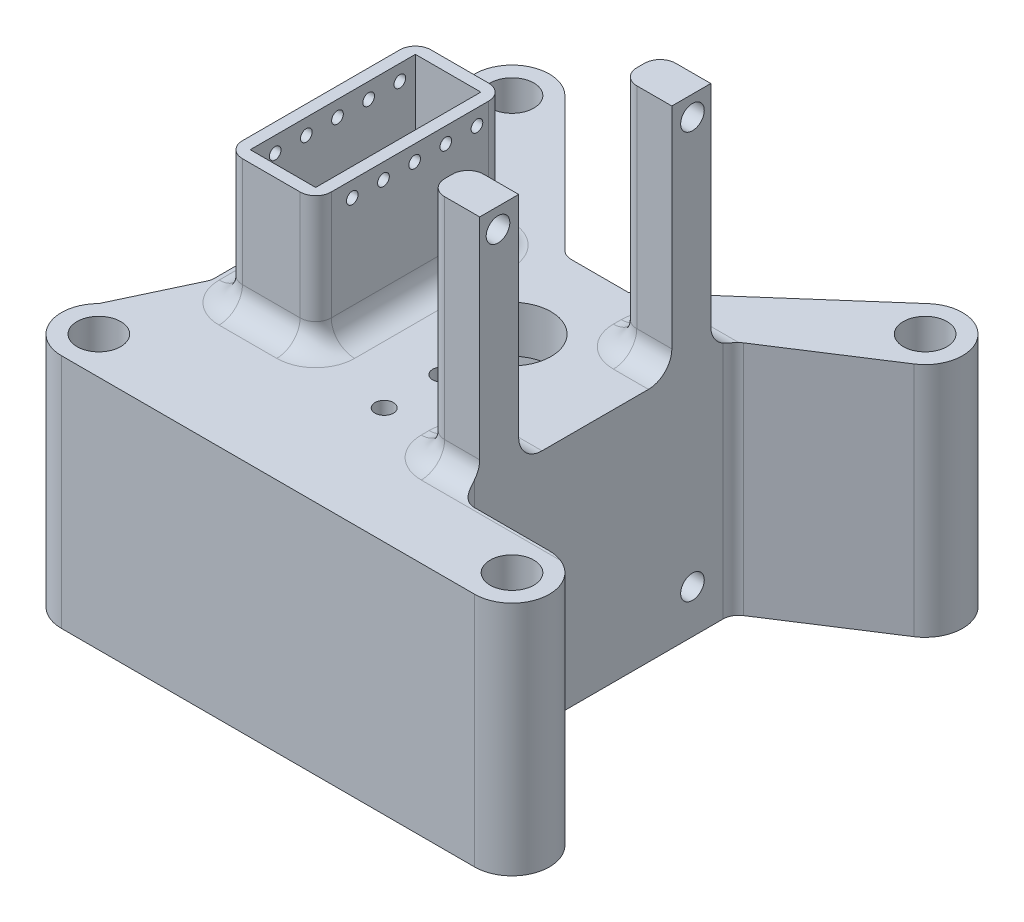
SolidWorks part; units mm, degrees
ref_plane "Front Plane" through (0, 0, 0) normal (0, 0, 1) x (1, 0, 0)
ref_plane "Top Plane" through (0, 0, 0) normal (0, 1, 0) x (1, 0, 0)
ref_plane "Right Plane" through (0, 0, 0) normal (1, 0, 0) x (0, 0, -1)
sketch "Sketch3" plane through (0, 0, 0) normal (0, 1, 0) x (1, 0, 0)
  line L0 (-33.676, -39.772) -> (33.676, -39.772)
  line L1 (-33.676, -33.676) -> (33.676, -33.676) construction
  line L2 (-33.676, -33.676) -> (-33.676, 33.676) construction
  line L3 (-33.676, 33.676) -> (33.676, 33.676) construction
  line L4 (33.676, -33.676) -> (33.676, 33.676) construction
  line L5 (-33.676, -33.676) -> (33.676, 33.676) construction
  line L6 (-33.676, 33.676) -> (33.676, -33.676) construction
  line L7 (10.033, -30.099) -> (-10.033, -30.099)
  line L8 (10.033, -30.099) -> (10.033, 10.033)
  line L9 (10.033, 10.033) -> (3.556, 10.033)
  line L10 (-10.033, -30.099) -> (-10.033, 10.033)
  line L11 (10.033, -30.099) -> (-10.033, 10.033) construction
  line L12 (10.033, 10.033) -> (-10.033, -30.099) construction
  line L13 (33.676, -27.58) -> (18.923, -27.58)
  line L14 (-3.556, 15.367) -> (3.556, 15.367) construction
  line L15 (-3.556, 15.367) -> (-3.556, 10.033)
  line L16 (0, 10.033) -> (3.556, 10.033) construction
  line L17 (3.556, 15.367) -> (3.556, 10.033)
  line L18 (-3.556, 15.367) -> (3.556, 10.033) construction
  line L19 (-3.556, 10.033) -> (3.556, 15.367) construction
  line L20 (-25.781, 10.033) -> (-15.113, 10.033) construction
  line L21 (-25.781, 10.033) -> (-25.781, -16.891) construction
  line L22 (-25.781, -16.891) -> (-15.113, -16.891) construction
  line L23 (-15.113, 10.033) -> (-15.113, -16.891) construction
  line L24 (-25.781, 10.033) -> (-15.113, -16.891) construction
  line L25 (-25.781, -16.891) -> (-15.113, 10.033) construction
  line L26 (18.923, -27.58) -> (18.923, 16.87)
  line L27 (36.9874, 28.5578) -> (18.923, 16.87)
  line L28 (29.6563, 38.259) -> (3.556, 15.367)
  line L31 (0, 10.033) -> (-3.556, 10.033) construction
  line L32 (-29.3669, 37.9879) -> (-6.731, 15.367)
  line L33 (-6.731, 15.367) -> (-3.556, 15.367)
  line L34 (-3.556, 10.033) -> (-10.033, 10.033)
  line L35 (-3.556, 10.033) -> (0, 10.033) construction
  line L36 (3.556, 10.033) -> (0, 10.033) construction
  line L37 (-32.131, -16.891) -> (-32.131, 10.033)
  line L38 (34.003, -24.1637) -> (18.923, -24.1637) construction
  line L39 (34.003, -24.1637) -> (34.003, 13.4537) construction
  line L40 (34.003, 13.4537) -> (18.923, 13.4537) construction
  line L41 (18.923, -24.1637) -> (18.923, 13.4537) construction
  line L42 (34.003, -24.1637) -> (18.923, 13.4537) construction
  line L43 (34.003, 13.4537) -> (18.923, -24.1637) construction
  line L44 (-32.131, 10.033) -> (-39.4519, 31.7268)
  line L45 (-32.131, -16.891) -> (-37.9865, -29.3654)
  circle A0 centre (-33.676, 33.676) radius 3.556
  circle A1 centre (33.676, 33.676) radius 3.556
  circle A2 centre (33.676, -33.676) radius 3.556
  circle A3 centre (-33.676, -33.676) radius 3.556
  circle A4 centre (0, 0) radius 6.35 construction
  circle A5 centre (0, 0) radius 10.033 construction
  circle A6 centre (0, 0) radius 63.5 construction
  arc A7 (33.676, -39.772) -> (33.676, -27.58) centre (33.676, -33.676) ccw
  arc A8 (-39.772, -33.676) -> (-33.676, -39.772) centre (-33.676, -33.676) ccw
  arc A9 (-29.3669, 37.9879) -> (-39.772, 33.676) centre (-33.676, 33.676) ccw
  arc A10 (36.9874, 28.5578) -> (29.6563, 38.259) centre (33.676, 33.676) ccw
  arc A11 (27.58, 33.676) -> (29.3654, 29.3654) centre (33.676, 33.676) ccw construction
  arc A12 (29.6563, 38.259) -> (27.58, 33.676) centre (33.676, 33.676) ccw construction
  arc A13 (29.3654, 29.3654) -> (33.676, 27.58) centre (33.676, 33.676) ccw construction
  arc A14 (33.676, 27.58) -> (36.9874, 28.5578) centre (33.676, 33.676) ccw construction
  arc A15 (-27.58, 33.676) -> (-29.3669, 37.9879) centre (-33.676, 33.676) ccw construction
  arc A16 (-29.3654, 29.3654) -> (-27.58, 33.676) centre (-33.676, 33.676) ccw construction
  arc A17 (-33.676, 27.58) -> (-29.3654, 29.3654) centre (-33.676, 33.676) ccw construction
  arc A18 (-39.772, 33.676) -> (-39.4519, 31.7268) centre (-33.676, 33.676) ccw
  arc A19 (-37.9865, -29.3654) -> (-39.772, -33.676) centre (-33.676, -33.676) ccw
  arc A20 (-29.3654, -29.3654) -> (-33.676, -27.58) centre (-33.676, -33.676) ccw construction
  arc A21 (-27.58, -33.676) -> (-29.3654, -29.3654) centre (-33.676, -33.676) ccw construction
  arc A22 (-33.676, -39.772) -> (-27.58, -33.676) centre (-33.676, -33.676) ccw construction
  arc A23 (33.676, -27.58) -> (29.3654, -29.3654) centre (33.676, -33.676) ccw construction
  arc A24 (29.3654, -29.3654) -> (27.58, -33.676) centre (33.676, -33.676) ccw construction
  arc A25 (27.58, -33.676) -> (33.676, -39.772) centre (33.676, -33.676) ccw construction
  arc A26 (-39.4519, 31.7268) -> (-33.676, 27.58) centre (-33.676, 33.676) ccw construction
  arc A27 (-33.676, -27.58) -> (-37.9865, -29.3654) centre (-33.676, -33.676) ccw construction
  point P0 (0, 0)
  point P10 (0, -10.033)
  point P25 (0, 12.7)
  point P30 (3.556, 12.7)
  point P32 (-20.447, -3.429)
  point P53 (18.923, -5.355)
  point P55 (26.463, -5.355)
  point P64 (-32.131, -3.429)
  dimension "D2" = 7.112
  dimension "D5" = 12.7
  dimension "D6" = 127
  dimension "D1" = 95.25
  dimension "D3" = 40.132
  dimension "D4" = 20.066
  dimension "D7" = 2.54
  dimension "D8" = 5.334
  dimension "D9" = 7.112
  dimension "D10" = 10.668
  dimension "D11" = 26.924
  dimension "D12" = 5.08
  dimension "D13" = 8.89
  dimension "D14" = 171.65
  dimension "D15" = 352.506
  dimension "D16" = 44.45
  dimension "D17" = 37.6174
  dimension "D18" = 3.175
  dimension "D19" = 30.16
  dimension "D21" = 6.35
  dimension "D20" = 67.3519
extrude "Boss-Extrude1" add sketch "Sketch3" along normal blind 21.463
sketch "Sketch4" plane through (0, 21.463, 0) normal (0, 1, 0) x (1, 0, 0)
  line L0 (-3.556, 15.367) -> (3.556, 15.367) construction
  line L1 (-3.556, 10.033) -> (3.556, 10.033) construction
  line L2 (3.556, 15.367) -> (-3.556, 15.367)
  line L3 (-3.556, 10.033) -> (3.556, 10.033)
  line L16 (-10.033, 10.033) -> (-3.556, 10.033)
  line L17 (-3.556, 10.033) -> (-3.556, 15.367)
  line L18 (-3.556, 15.367) -> (-6.731, 15.367)
  line L19 (-6.731, 15.367) -> (-29.3669, 37.9879)
  line L20 (-39.4519, 31.7268) -> (-32.131, 10.033)
  line L21 (-33.676, -39.772) -> (33.676, -39.772)
  line L22 (33.676, -27.58) -> (18.923, -27.58)
  line L23 (18.923, -27.58) -> (18.923, 16.87)
  line L24 (18.923, 16.87) -> (36.9874, 28.5578)
  line L25 (29.6563, 38.259) -> (3.556, 15.367)
  line L27 (3.556, 15.367) -> (3.556, 10.033)
  line L28 (3.556, 10.033) -> (10.033, 10.033)
  line L29 (10.033, 10.033) -> (10.033, -30.099)
  line L30 (10.033, -30.099) -> (-10.033, -30.099)
  line L31 (-10.033, -30.099) -> (-10.033, 10.033)
  line L32 (-10.033, 10.033) -> (-3.556, 10.033)
  line L33 (-3.556, 10.033) -> (-3.556, 15.367) construction
  line L34 (-3.556, 15.367) -> (-6.731, 15.367)
  line L35 (-6.731, 15.367) -> (-29.3669, 37.9879)
  line L37 (-33.676, -39.772) -> (33.676, -39.772)
  line L38 (33.676, -27.58) -> (18.923, -27.58)
  line L39 (18.923, -27.58) -> (18.923, 16.87)
  line L40 (18.923, 16.87) -> (36.9874, 28.5578)
  line L41 (29.6563, 38.259) -> (3.556, 15.367)
  line L43 (3.556, 15.367) -> (3.556, 10.033) construction
  line L44 (3.556, 10.033) -> (10.033, 10.033)
  line L45 (10.033, 10.033) -> (10.033, -30.099)
  line L46 (10.033, -30.099) -> (-10.033, -30.099)
  line L47 (-10.033, -30.099) -> (-10.033, 10.033)
  line L52 (-39.4519, 31.7268) -> (-32.131, 10.033)
  line L53 (-32.131, 10.033) -> (-32.131, -16.891)
  line L54 (-32.131, 10.033) -> (-32.131, -16.891)
  line L55 (-32.131, -16.891) -> (-37.9865, -29.3654)
  line L56 (-32.131, -16.891) -> (-37.9865, -29.3654)
  circle A3 centre (33.676, -33.676) radius 3.556 construction
  arc A4 (-29.3669, 37.9879) -> (-39.4519, 31.7268) centre (-33.676, 33.676) ccw
  arc A5 (-37.9865, -29.3654) -> (-33.676, -39.772) centre (-33.676, -33.676) ccw
  arc A6 (33.676, -39.772) -> (33.676, -27.58) centre (33.676, -33.676) ccw
  arc A7 (36.9874, 28.5578) -> (29.6563, 38.259) centre (33.676, 33.676) ccw
  arc A8 (-29.3669, 37.9879) -> (-39.4519, 31.7268) centre (-33.676, 33.676) ccw
  arc A9 (-37.9865, -29.3654) -> (-33.676, -39.772) centre (-33.676, -33.676) ccw
  arc A10 (33.676, -39.772) -> (33.676, -27.58) centre (33.676, -33.676) ccw
  arc A11 (36.9874, 28.5578) -> (29.6563, 38.259) centre (33.676, 33.676) ccw
  circle A12 centre (33.676, -33.676) radius 3.556
  circle A13 centre (33.676, 33.676) radius 3.556 construction
  circle A14 centre (33.676, 33.676) radius 3.556
  circle A15 centre (-33.676, 33.676) radius 3.556 construction
  circle A16 centre (-33.676, 33.676) radius 3.556
  circle A17 centre (-33.676, -33.676) radius 3.556 construction
  circle A18 centre (-33.676, -33.676) radius 3.556
  dimension "D1" = 0
extrude "Boss-Extrude2" add sketch "Sketch4" along normal blind 7.366
sketch "Sketch5" plane through (0, 28.829, 0) normal (0, 1, 0) x (1, 0, 0)
  line L8 (3.556, 15.367) -> (-6.731, 15.367)
  line L9 (-6.731, 15.367) -> (-29.3669, 37.9879)
  line L10 (-39.4519, 31.7268) -> (-32.131, 10.033)
  line L11 (-33.676, -39.772) -> (33.676, -39.772)
  line L12 (33.676, -27.58) -> (18.923, -27.58)
  line L13 (18.923, -27.58) -> (18.923, 16.87)
  line L14 (18.923, 16.87) -> (36.9874, 28.5578)
  line L15 (29.6563, 38.259) -> (3.556, 15.367)
  line L16 (3.556, 15.367) -> (-6.731, 15.367)
  line L17 (-6.731, 15.367) -> (-29.3669, 37.9879)
  line L19 (-33.676, -39.772) -> (33.676, -39.772)
  line L20 (33.676, -27.58) -> (18.923, -27.58)
  line L21 (18.923, -27.58) -> (18.923, 16.87)
  line L22 (18.923, 16.87) -> (36.9874, 28.5578)
  line L23 (29.6563, 38.259) -> (3.556, 15.367)
  line L26 (-39.4519, 31.7268) -> (-32.131, 10.033)
  line L27 (-32.131, 10.033) -> (-32.131, -16.891)
  line L28 (-32.131, 10.033) -> (-32.131, -16.891)
  line L29 (-32.131, -16.891) -> (-37.9865, -29.3654)
  line L30 (-32.131, -16.891) -> (-37.9865, -29.3654)
  circle A0 centre (0, 0) radius 6.35 construction
  circle A1 centre (33.676, 33.676) radius 3.556
  circle A2 centre (33.676, 33.676) radius 3.556
  circle A3 centre (-33.676, 33.676) radius 3.556
  circle A4 centre (-33.676, 33.676) radius 3.556
  circle A5 centre (-33.676, -33.676) radius 3.556
  circle A6 centre (-33.676, -33.676) radius 3.556
  circle A7 centre (33.676, -33.676) radius 3.556
  circle A8 centre (33.676, -33.676) radius 3.556
  circle A9 centre (0, 0) radius 6.35
  arc A12 (-29.3669, 37.9879) -> (-39.4519, 31.7268) centre (-33.676, 33.676) ccw
  arc A13 (-37.9865, -29.3654) -> (-33.676, -39.772) centre (-33.676, -33.676) ccw
  arc A14 (33.676, -39.772) -> (33.676, -27.58) centre (33.676, -33.676) ccw
  arc A15 (36.9874, 28.5578) -> (29.6563, 38.259) centre (33.676, 33.676) ccw
  arc A16 (-29.3669, 37.9879) -> (-39.4519, 31.7268) centre (-33.676, 33.676) ccw
  arc A17 (-37.9865, -29.3654) -> (-33.676, -39.772) centre (-33.676, -33.676) ccw
  arc A18 (33.676, -39.772) -> (33.676, -27.58) centre (33.676, -33.676) ccw
  arc A19 (36.9874, 28.5578) -> (29.6563, 38.259) centre (33.676, 33.676) ccw
  dimension "D1" = 0
  dimension "D2" = 0
  dimension "D3" = 0
  dimension "D4" = 0
  dimension "D5" = 0
extrude "Boss-Extrude3" add sketch "Sketch5" along normal blind 7.62
sketch "Sketch6" plane through (0, 36.449, 0) normal (0, 1, 0) x (1, 0, 0)
  line L0 (-25.781, 10.033) -> (-25.781, -16.891) construction
  line L1 (-25.781, -16.891) -> (-15.113, -16.891) construction
  line L2 (-15.113, 10.033) -> (-15.113, -16.891) construction
  line L3 (-25.781, 10.033) -> (-15.113, 10.033) construction
  line L4 (-25.781, 10.033) -> (-25.781, -16.891) construction
  line L5 (-25.781, -16.891) -> (-15.113, -16.891) construction
  line L6 (-15.113, 10.033) -> (-15.113, -16.891) construction
  line L7 (-25.781, 10.033) -> (-15.113, 10.033) construction
  line L9 (-13.208, 11.938) -> (-27.686, 11.938)
  line L10 (-13.208, 11.938) -> (-13.208, -18.796)
  line L11 (-13.208, -18.796) -> (-27.686, -18.796)
  line L12 (-27.686, 11.938) -> (-27.686, -18.796)
  line L13 (-13.208, 11.938) -> (-27.686, -18.796) construction
  line L14 (-13.208, -18.796) -> (-27.686, 11.938) construction
  point P4 (-20.447, -3.429)
  point P11 (-20.447, -16.891)
  dimension "D1" = 1.905
  dimension "D2" = 1.905
extrude "Boss-Extrude4" add sketch "Sketch6" along normal blind 21.59
sketch "Sketch7" plane through (0, 58.039, 0) normal (0, 1, 0) x (1, 0, 0)
  line L0 (-25.781, 10.033) -> (-25.781, -16.891) construction
  line L1 (-25.781, -16.891) -> (-15.113, -16.891) construction
  line L2 (-15.113, 10.033) -> (-15.113, -16.891) construction
  line L3 (-25.781, 10.033) -> (-15.113, 10.033) construction
  line L4 (-25.781, 10.033) -> (-25.781, -16.891)
  line L5 (-25.781, -16.891) -> (-15.113, -16.891)
  line L6 (-15.113, 10.033) -> (-15.113, -16.891)
  line L7 (-25.781, 10.033) -> (-15.113, 10.033)
extrude "Cut-Extrude1" cut sketch "Sketch7" against normal blind 50.8
sketch "Sketch8" plane through (-27.686, 0, 0) normal (-1, 0, 0) x (0, 0, 1)
  line L0 (16.891, 7.239) -> (16.891, 58.039) construction
  line L1 (-10.033, 7.239) -> (-10.033, 58.039) construction
  line L2 (16.891, 7.239) -> (16.891, 58.039) construction
  line L3 (-10.033, 7.239) -> (-10.033, 58.039) construction
  line L4 (-7.493, 55.499) -> (-2.413, 55.499) construction
  circle A0 centre (-7.493, 55.499) radius 0.9525
  circle A1 centre (-2.413, 55.499) radius 0.9525
  circle A2 centre (2.667, 55.499) radius 0.9525
  circle A3 centre (7.747, 55.499) radius 0.9525
  circle A4 centre (12.827, 55.499) radius 0.9525
  dimension "D1" = 1.905
  dimension "D5" = 5.08
  dimension "D2" = 2.54
  dimension "D3" = 2.54
  dimension "D4" = 5
extrude "Cut-Extrude2" cut sketch "Sketch8" against normal through all
sketch "Sketch10" plane through (0, 36.449, 0) normal (0, 1, 0) x (1, 0, 0)
  line L0 (18.923, -27.58) -> (18.923, 16.87) construction
  line L1 (10.668, -24.19) -> (18.923, -24.19)
  line L2 (10.668, -24.19) -> (10.668, -17.84)
  line L3 (10.668, 13.48) -> (18.923, 13.48)
  line L4 (18.923, -24.19) -> (18.923, -17.84)
  line L5 (10.668, -24.19) -> (18.923, 13.48) construction
  line L6 (10.668, 13.48) -> (18.923, -24.19) construction
  line L7 (18.923, -27.58) -> (18.923, 16.87) construction
  line L8 (18.923, -17.84) -> (18.923, 7.13) construction
  line L9 (18.923, -17.84) -> (10.668, -17.84)
  line L10 (18.923, -17.84) -> (18.923, 7.13) construction
  line L11 (18.923, 7.13) -> (10.668, 7.13)
  line L12 (10.668, -17.84) -> (10.668, 7.13) construction
  line L13 (18.923, -17.84) -> (10.668, 7.13) construction
  line L14 (18.923, 7.13) -> (10.668, -17.84) construction
  line L15 (18.923, 7.13) -> (18.923, 13.48)
  line L16 (10.668, -17.84) -> (10.668, 7.13) construction
  line L17 (10.668, 7.13) -> (10.668, 13.48)
  point P0 (14.7955, -5.355)
  point P7 (18.923, -5.355)
  point P9 (14.7955, -5.355)
  dimension "D1" = 37.67
  dimension "D2" = 8.255
  dimension "D3" = 6.35
extrude "Boss-Extrude5" add sketch "Sketch10" along normal blind 38.1
sketch "Sketch9" plane through (18.923, 0, 0) normal (1, 0, 0) x (0, 0, -1)
  line L0 (-27.58, 0) -> (16.87, 0) construction
  line L1 (-21.205, 71.3) -> (10.495, 71.3) construction
  line L2 (-21.205, 71.3) -> (-21.205, 5) construction
  line L3 (-21.205, 5) -> (10.495, 5) construction
  line L4 (10.495, 71.3) -> (10.495, 5) construction
  line L5 (-21.205, 71.3) -> (10.495, 5) construction
  line L6 (-21.205, 5) -> (10.495, 71.3) construction
  circle A0 centre (-21.205, 71.3) radius 1.925
  circle A1 centre (10.495, 71.3) radius 1.925
  circle A2 centre (10.495, 5) radius 1.925
  circle A3 centre (-21.205, 5) radius 1.925
  point P0 (-5.355, 38.15)
  dimension "D4" = 3.85
  dimension "D1" = 31.7
  dimension "D2" = 66.3
  dimension "D3" = 5
extrude "Cut-Extrude3" cut sketch "Sketch9" against normal blind 5.75
sketch "Sketch13" plane through (0, 36.449, 0) normal (0, 1, 0) x (1, 0, 0)
  line L0 (0, -11.43) -> (0, -20.828) construction
  circle A0 centre (0, -11.43) radius 1.5
  circle A1 centre (0, -20.828) radius 1.5
  dimension "D2" = 3
  dimension "D1" = 9.398
  dimension "D3" = 11.43
extrude "Cut-Extrude4" cut sketch "Sketch13" against normal blind 4
fillet "Fillet1" radius 2.54 13 edges at (10.668, 55.499, 17.84) (10.668, 55.499, 24.19) (10.668, 55.499, -7.13) (10.668, 55.499, -13.48) (-27.686, 47.244, -11.938) (-13.208, 47.244, -11.938) (-13.208, 47.244, 18.796) (-27.686, 47.244, 18.796) (-32.131, 18.2245, 16.891) (-32.131, 18.2245, -10.033) (-6.731, 18.2245, -15.367) (18.923, 18.2245, -16.87) (18.923, 18.2245, 27.58)
fillet "Fillet2" radius 3.81 18 edges at (-13.9519, 36.449, -11.1941) (-13.208, 36.449, 3.429) (-13.9519, 36.449, 18.0521) (-20.447, 36.449, 18.796) (-26.9421, 36.449, 18.0521) (-27.686, 36.449, 3.429) (-26.9421, 36.449, -11.1941) (16.0655, 36.449, 24.19) (11.4119, 36.449, 23.446) (10.668, 36.449, 21.015) (11.4119, 36.449, 18.5839) (16.0655, 36.449, -7.13) (11.4119, 36.449, -7.874) (10.668, 36.449, -10.305) (11.4119, 36.449, -12.7361) (-20.447, 36.449, -11.938) (16.0655, 36.449, 17.84) (16.0655, 36.449, -13.48)
sketch "Sketch14" plane through (0, 0, 0) normal (0, -1, 0) x (1, 0, 0)
  line L17 (-3.556, -10.033) -> (-10.033, -10.033)
  line L18 (-10.033, -10.033) -> (-10.033, 30.099)
  line L19 (-10.033, 30.099) -> (10.033, 30.099)
  line L20 (10.033, 30.099) -> (10.033, -10.033)
  line L21 (10.033, -10.033) -> (3.556, -10.033)
  line L22 (3.556, -10.033) -> (3.556, -15.367)
  line L23 (3.556, -15.367) -> (29.6563, -38.259)
  line L24 (36.9874, -28.5578) -> (20.0832, -17.6207)
  line L25 (18.923, -15.4881) -> (18.923, 25.04)
  line L26 (21.463, 27.58) -> (33.676, 27.58)
  line L27 (33.676, 39.772) -> (-33.676, 39.772)
  line L28 (-37.9865, 29.3654) -> (-32.3717, 17.4038)
  line L29 (-32.131, 16.3245) -> (-32.131, -9.616)
  line L30 (-32.2643, -10.4281) -> (-39.4519, -31.7268)
  line L31 (-29.3669, -37.9879) -> (-7.4748, -16.1104)
  line L32 (-5.6794, -15.367) -> (-3.556, -15.367)
  line L33 (-3.556, -15.367) -> (-3.556, -10.033)
  line L34 (-3.556, -10.033) -> (-10.033, -10.033)
  line L35 (-10.033, -10.033) -> (-10.033, 30.099)
  line L36 (-10.033, 30.099) -> (10.033, 30.099)
  line L37 (10.033, 30.099) -> (10.033, -10.033)
  line L38 (10.033, -10.033) -> (3.556, -10.033)
  line L39 (3.556, -10.033) -> (3.556, -15.367)
  line L40 (3.556, -15.367) -> (29.6563, -38.259)
  line L41 (36.9874, -28.5578) -> (20.0832, -17.6207)
  line L42 (18.923, -15.4881) -> (18.923, 25.04)
  line L43 (21.463, 27.58) -> (33.676, 27.58)
  line L44 (33.676, 39.772) -> (-33.676, 39.772)
  line L45 (-37.9865, 29.3654) -> (-32.3717, 17.4038)
  line L46 (-32.131, 16.3245) -> (-32.131, -9.616)
  line L47 (-32.2643, -10.4281) -> (-39.4519, -31.7268)
  line L48 (-29.3669, -37.9879) -> (-7.4748, -16.1104)
  line L49 (-5.6794, -15.367) -> (-3.556, -15.367)
  line L50 (-3.556, -15.367) -> (-3.556, -10.033)
  circle A0 centre (-33.676, -33.676) radius 3.556 construction
  circle A1 centre (-33.676, -33.676) radius 3.556
  circle A2 centre (-33.676, 33.676) radius 3.556 construction
  circle A3 centre (-33.676, 33.676) radius 3.556
  circle A4 centre (33.676, 33.676) radius 3.556 construction
  circle A5 centre (33.676, 33.676) radius 3.556
  circle A6 centre (33.676, -33.676) radius 3.556 construction
  circle A7 centre (33.676, -33.676) radius 3.556
  arc A9 (29.6563, -38.259) -> (36.9874, -28.5578) centre (33.676, -33.676) ccw
  arc A10 (18.923, -15.4881) -> (20.0832, -17.6207) centre (21.463, -15.4881) ccw
  arc A11 (21.463, 27.58) -> (18.923, 25.04) centre (21.463, 25.04) ccw
  arc A12 (33.676, 27.58) -> (33.676, 39.772) centre (33.676, 33.676) ccw
  arc A13 (-33.676, 39.772) -> (-37.9865, 29.3654) centre (-33.676, 33.676) ccw
  arc A14 (-32.131, 16.3245) -> (-32.3717, 17.4038) centre (-34.671, 16.3245) ccw
  arc A15 (-32.2643, -10.4281) -> (-32.131, -9.616) centre (-34.671, -9.616) ccw
  arc A16 (-39.4519, -31.7268) -> (-29.3669, -37.9879) centre (-33.676, -33.676) ccw
  arc A17 (-5.6794, -15.367) -> (-7.4748, -16.1104) centre (-5.6794, -17.907) ccw
  arc A18 (29.6563, -38.259) -> (36.9874, -28.5578) centre (33.676, -33.676) ccw
  arc A19 (18.923, -15.4881) -> (20.0832, -17.6207) centre (21.463, -15.4881) ccw
  arc A20 (21.463, 27.58) -> (18.923, 25.04) centre (21.463, 25.04) ccw
  arc A21 (33.676, 27.58) -> (33.676, 39.772) centre (33.676, 33.676) ccw
  arc A22 (-33.676, 39.772) -> (-37.9865, 29.3654) centre (-33.676, 33.676) ccw
  arc A23 (-32.131, 16.3245) -> (-32.3717, 17.4038) centre (-34.671, 16.3245) ccw
  arc A24 (-32.2643, -10.4281) -> (-32.131, -9.616) centre (-34.671, -9.616) ccw
  arc A25 (-39.4519, -31.7268) -> (-29.3669, -37.9879) centre (-33.676, -33.676) ccw
  arc A26 (-5.6794, -15.367) -> (-7.4748, -16.1104) centre (-5.6794, -17.907) ccw
  dimension "D1" = 0
extrude "Boss-Extrude6" add sketch "Sketch14" along normal blind 2.0585
equation "\"AIRFRAME_OD\"= 5.15in"
equation "\"AIRFRAME_ID\"= 5.00in"
equation "\"FLAT_T\"= 0.125in"
equation "\"COUPLER_OD\"= 4.998in"
equation "\"COUPLER_ID\"= 4.88in"
equation "\"NOSE_EXP_L\"= 27in"
equation "\"NOSE_SHOULDER_L\"= 5in"
equation "\"MAIN_L\"= 30in"
equation "\"RECO_COUP_L\"= 10in"
equation "\"RECO_SWITCH_L\"= 2in"
equation "\"RECO_ROD_X\"= 3.5in"
equation "\"DROGUE_L\"= 20in"
equation "\"ATS_FORE_COUP_L\"= 5.5in"
equation "\"ATS_AFT_COUP_L\"= 4.5in"
equation "\"ATS_ROD_X\"= 3.75in"
equation "\"LOWER_L\"= 30in"
equation "\"FIN_ROOT\"= 8in"
equation "\"FIN_X\"= 0.75in"
equation "\"FIN_N\"= 4"
equation "\"MOTOR_OD\"= 3.091in"
equation "\"MOTOR_ID\"= 3.00in"
equation "\"MOTOR_L\"= 14in"
equation "\"CR_AFT_X\"= 0.5in"
equation "\"CR_FORE_X\"= 9.25in"
equation "\"MOTOR_LOWER_X\"= 2in"
equation "\"D1@Sketch3\"=\"ATS_ROD_X\""
equation "\"D6@Sketch3\"=\"AIRFRAME_ID\""
